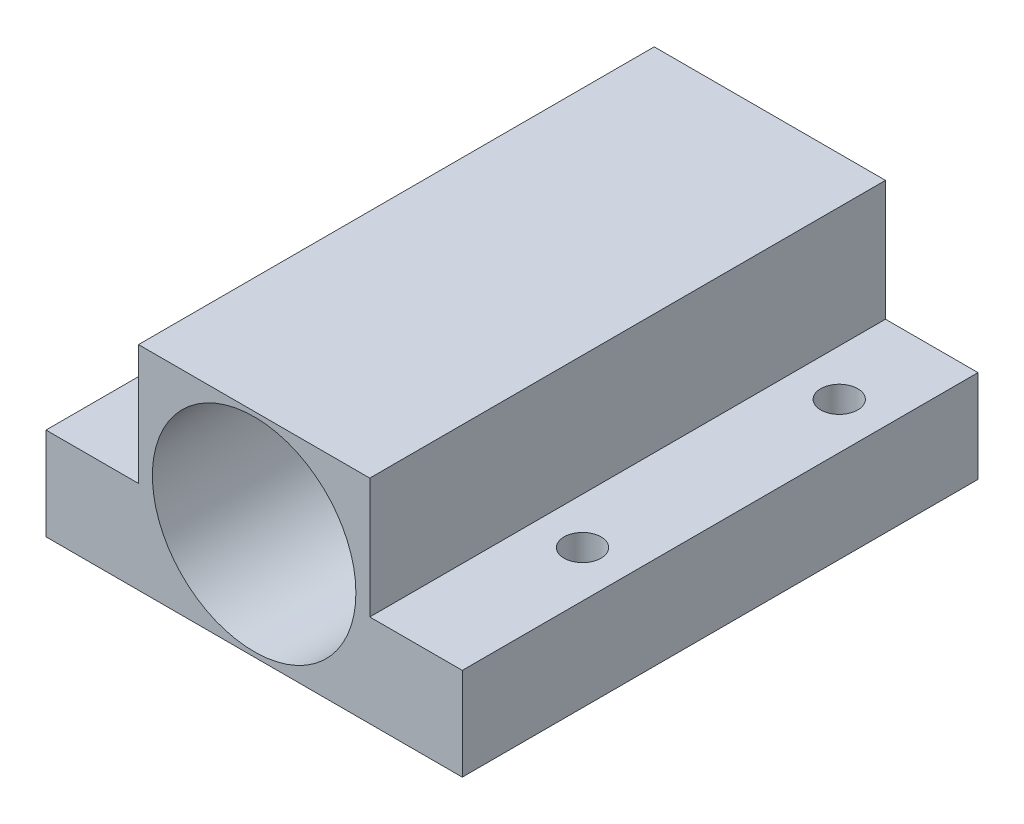
SolidWorks part; units mm, degrees
material "ABS"
ref_plane "Front Plane" through (0, 0, 0) normal (0, 0, 1) x (1, 0, 0)
ref_plane "Top Plane" through (0, 0, 0) normal (0, 1, 0) x (1, 0, 0)
ref_plane "Right Plane" through (0, 0, 0) normal (1, 0, 0) x (0, 0, -1)
sketch "Sketch1" plane through (0, 0, 0) normal (0, 0, 1) x (1, 0, 0)
  line L0 (-65.4098, -16.7) -> (184.5902, -16.7) construction
  line L1 (-12.5, 6.3) -> (12.5, 6.3)
  line L2 (-12.5, 6.3) -> (-12.5, -16.7)
  line L3 (-12.5, -16.7) -> (12.5, -16.7)
  line L4 (12.5, 6.3) -> (12.5, -16.7)
  line L5 (-12.5, 6.3) -> (12.5, -16.7) construction
  line L6 (-12.5, -16.7) -> (12.5, 6.3) construction
  line L7 (12.5, -16.7) -> (22.5, -16.7)
  line L8 (12.5, -16.7) -> (12.5, -6.7)
  line L9 (12.5, -6.7) -> (22.5, -6.7)
  line L10 (22.5, -16.7) -> (22.5, -6.7)
  line L11 (12.5, -16.7) -> (22.5, -6.7) construction
  line L12 (12.5, -6.7) -> (22.5, -16.7) construction
  line L13 (-12.5, -16.7) -> (-22.5, -16.7)
  line L14 (-12.5, -16.7) -> (-12.5, -6.7)
  line L15 (-12.5, -6.7) -> (-22.5, -6.7)
  line L16 (-22.5, -16.7) -> (-22.5, -6.7)
  line L17 (-12.5, -16.7) -> (-22.5, -6.7) construction
  line L18 (-12.5, -6.7) -> (-22.5, -16.7) construction
  circle A0 centre (0, -5.2) radius 4.1
  circle A1 centre (0, -5.2) radius 11
  point P8 (0, -5.2)
  point P14 (17.5, -11.7)
  point P16 (-17.5, -11.7)
  dimension "D4" = 8.2
  dimension "D5" = 22
  dimension "D11" = 11.5
  dimension "D2" = 0
  dimension "D3" = 25
  dimension "D6" = 10
  dimension "D7" = 10
  dimension "D8" = 10
  dimension "D9" = 10
  dimension "D10" = 12.5
  dimension "D12" = 11.5
  dimension "D13" = 5.2
extrude "Boss-Extrude1" add sketch "Sketch1" along normal up to surface (55.75 mm away) contours L4 L1 L2 L3 A1 | L16 L13 L2 L15 | L7 L10 L9 L4 region at (0, 5.9603, 0) region at (-17.5, -11.7, 0) region at (17.5, -11.7, 0)
sketch "Sketch2" plane through (0, -6.7, 0) normal (0, 1, 0) x (1, 0, 0)
  line L0 (-22.5, 0) -> (-12.5, -55.75)
  line L1 (-12.5, -55.75) -> (-22.5, -55.75)
  line L2 (-22.5, -55.75) -> (-12.5, 0)
  line L3 (12.5, 0) -> (22.5, -55.75)
  line L4 (22.5, -55.75) -> (22.5, 0)
  line L5 (22.5, 0) -> (12.5, -55.75)
  circle A0 centre (-17.5, -10) radius 2
  circle A1 centre (17.5, -10) radius 2
  circle A2 centre (17.5, -10) radius 2 construction
  circle A3 centre (-17.5, -10) radius 2 construction
  circle A4 centre (-17.5, -37.75) radius 2
  circle A5 centre (17.5, -37.75) radius 2
  circle A6 centre (17.5, -37.75) radius 2 construction
  circle A7 centre (-17.5, -37.75) radius 2 construction
  dimension "D1" = 4
  dimension "D2" = 4
extrude "Cut-Extrude1" cut sketch "Sketch2" against normal blind 9 contours A0 | A4 | A1 | A5
